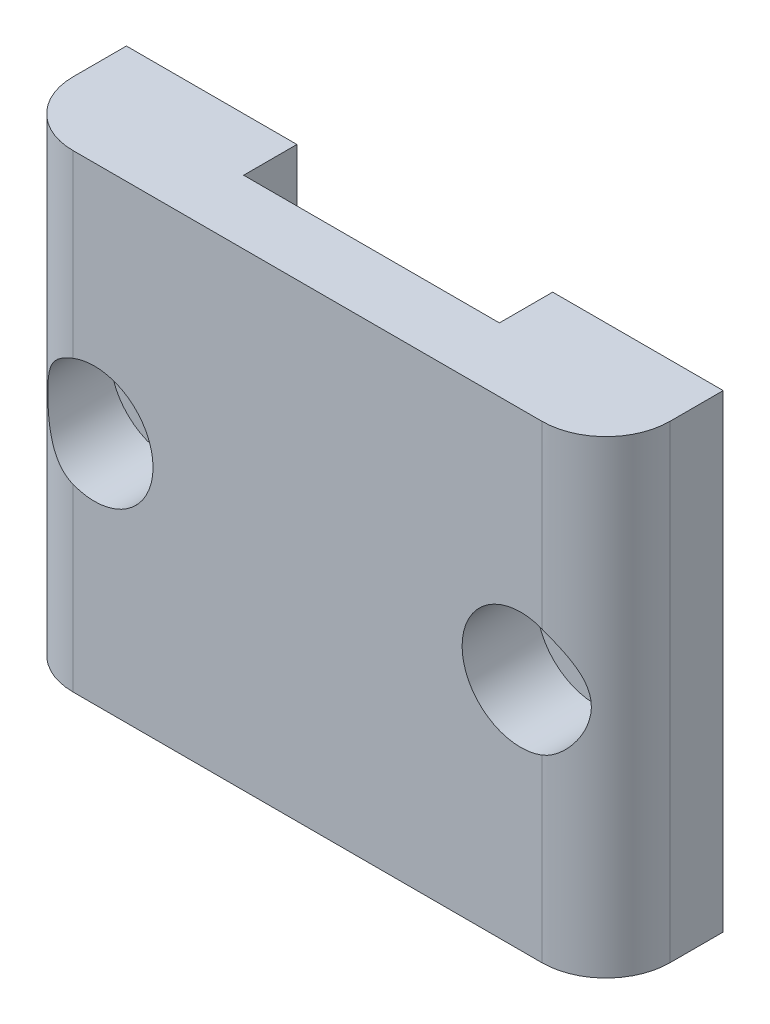
SolidWorks part; units mm, degrees
ref_plane "Front Plane" through (0, 0, 0) normal (0, 0, 1) x (1, 0, 0)
ref_plane "Top Plane" through (0, 0, 0) normal (0, 1, 0) x (1, 0, 0)
ref_plane "Right Plane" through (0, 0, 0) normal (1, 0, 0) x (0, 0, -1)
sketch "Sketch1" plane through (0, 0, 0) normal (0, 0, 1) x (1, 0, 0)
  line L1 (14, -11) -> (-14, -11)
  line L2 (14, -11) -> (14, 11)
  line L3 (14, 11) -> (-14, 11)
  line L4 (-14, -11) -> (-14, 11)
  line L5 (14, -11) -> (-14, 11) construction
  line L6 (14, 11) -> (-14, -11) construction
  point P0 (0, 0)
  dimension "D1" = 22
  dimension "D2" = 28
extrude "Boss-Extrude1" add sketch "Sketch1" against normal blind 3
sketch "Sketch2" plane through (0, 0, -3) normal (0, 0, -1) x (-1, 0, 0)
  line L0 (14, 11) -> (-6, 11)
  line L1 (14, 11) -> (-14, 11) construction
  line L2 (-6, 11) -> (-6, -11)
  line L3 (-14, -11) -> (14, -11) construction
  line L4 (-6, -11) -> (14, -11)
  line L5 (14, -11) -> (14, 11) construction
  line L6 (14, -11) -> (14, 11)
  line L7 (0, -3.5869) -> (0, 3.5869)
  line L8 (-14, -11) -> (-14, 11)
  line L9 (6, -11) -> (-14, -11)
  line L10 (6, 11) -> (6, -11)
  line L11 (-14, 11) -> (6, 11)
  point P15 (0, 0)
extrude "Boss-Extrude2" add sketch "Sketch2" along normal blind 2.5 contours L2 | L10 region at (-10, 0, -3) region at (10, 0, -3)
sketch "Sketch3" plane through (0, 0, -5.5) normal (0, 0, -1) x (-1, 0, 0)
  line L0 (-14, 0) -> (-10, 0)
  line L3 (-14, 11) -> (-14, -11) construction
  line L4 (-10, 0) -> (-10, 11)
  line L6 (-6, 11) -> (-14, 11) construction
  line L7 (0, -2.7261) -> (0, 2.7261)
  circle A2 centre (-10, 0) radius 1.6
  circle A3 centre (10, 0) radius 1.6
  point P13 (0, 0)
extrude "Cut-Extrude1" cut sketch "Sketch3" against normal through all contours A2 | A3
sketch "Sketch4" plane through (0, 0, 0) normal (0, 0, 1) x (1, 0, 0)
  circle A0 centre (-10, 0) radius 2.75
  circle A1 centre (10, 0) radius 2.75
  point P6 (10, 0)
  point P7 (10, 0)
  point P8 (0, 0)
  point P10 (-10, 0)
extrude "Cut-Extrude2" cut sketch "Sketch4" against normal blind 3.5
fillet "Fillet1" radius 3 2 edges at (-14, 0, 0) (14, 0, 0)
